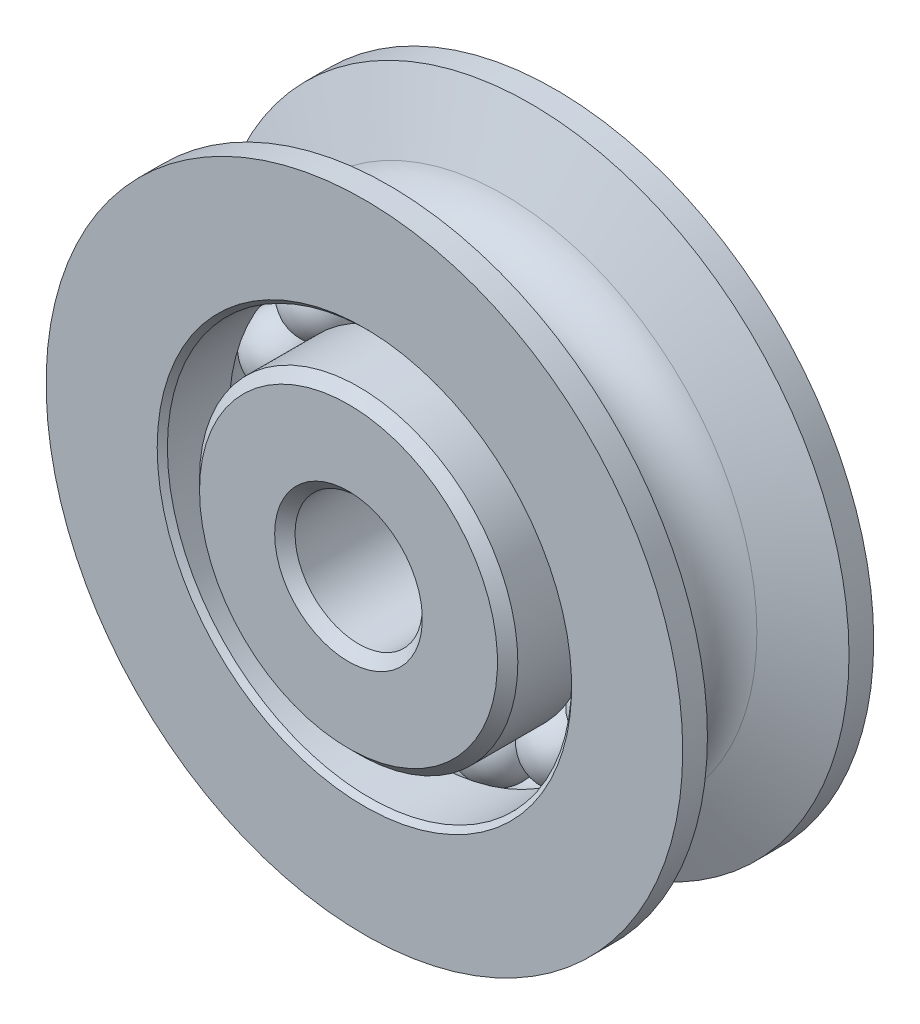
SolidWorks part; units mm, degrees
ref_plane "Front" through (0, 0, 0) normal (0, 0, 1) x (1, 0, 0)
ref_plane "Top" through (0, 0, 0) normal (0, 1, 0) x (1, 0, 0)
ref_plane "Right" through (0, 0, 0) normal (1, 0, 0) x (0, 0, -1)
sketch "Sketch1" plane through (0, 0, 0) normal (1, 0, 0) x (0, 0, -1)
  line L0 (3.5306, 15.875) -> (4.7625, 15.875)
  line L1 (-3.5306, 15.875) -> (-4.7625, 15.875)
  line L2 (-3.5306, 15.875) -> (-2.2078, 12.6016)
  line L3 (1.4287, 10.0806) -> (4.7625, 10.0806)
  line L4 (5.5562, 3.175) -> (-5.5562, 3.175)
  line L5 (-1.4287, 7.9375) -> (-5.5563, 7.9375)
  line L6 (3.5306, 15.875) -> (2.2078, 12.6016)
  line L8 (-5.5562, 0) -> (5.5562, 0) construction
  line L10 (4.7625, 15.875) -> (4.7625, 10.0806)
  line L13 (-5.5563, 7.9375) -> (-5.5562, 3.175)
  line L14 (0, 11.1125) -> (0, -11.1125) construction
  line L16 (5.5563, 7.9375) -> (5.5562, 3.175)
  line L17 (-4.7625, 15.875) -> (-4.7625, -15.875) construction
  line L18 (-4.7625, 10.0806) -> (-1.4287, 10.0806)
  line L20 (5.5563, 7.9375) -> (1.4287, 7.9375)
  line L21 (-4.7625, 10.0806) -> (-4.7625, 15.875)
  arc A0 (-2.2078, 12.6016) -> (2.2078, 12.6016) centre (0, 13.4938) ccw
  circle A1 centre (0, 13.4938) radius 2.3813 construction
  circle A2 centre (0, 0) radius 3.175 construction
  circle A3 centre (0, 0) radius 7.9375 construction
  arc A4 (-1.4287, 7.9375) -> (1.4287, 7.9375) centre (0, 9.0091) ccw
  circle A5 centre (0, -13.4937) radius 2.3813 construction
  arc A6 (1.4287, 10.0806) -> (-1.4287, 10.0806) centre (0, 9.0091) ccw
  point P28 (-4.7625, 0)
  dimension "Rope Dia" = 4.7625
  dimension "D1" = 15.875
  dimension "Shaft Dia" = 6.35
  dimension "D3" = 2.1431
  dimension "D2" = 3.5719
  dimension "Wd" = 11.1125
  dimension "D8" = 1.2319
  dimension "Groove Dia" = 22.225
  dimension "OD" = 31.75
  dimension "w Wd" = 9.525
revolve "Revolve1" add sketch "Sketch1" angle 360 about L8
sketch "Sketch2" plane through (0, 0, 0) normal (1, 0, 0) x (0, 0, -1)
  line L0 (0, 11.1125) -> (0, -11.1125) construction
  line L1 (0, 10.795) -> (0, 7.2231)
  arc A0 (1.4287, 10.0806) -> (-1.4287, 10.0806) centre (0, 9.0091) ccw construction
  arc A1 (0, 7.2231) -> (0, 10.795) centre (0, 9.0091) ccw
revolve "Revolve2" add sketch "Sketch2" angle 360 about L1
pattern_circular "CirPattern1" count 15 over 360 of bodies 117
chamfer "Chamfer1" distance 0.508 angle 45 4 edges at (3.175, 0, -5.5562) (7.9375, 0, -5.5563) (7.9375, 0, 5.5563) (3.175, 0, 5.5562)
chamfer "Chamfer2" distance 0.254 angle 45 2 edges at (10.0806, 0, -4.7625) (10.0806, 0, 4.7625)
equation "\"D1@Sketch1\" = \"Shaft Dia@Sketch1\" * 2.5"
equation "\"D2@Sketch1\" = \"Rope Dia@Sketch1\" * .75"
equation "\"D3@Sketch1\" = \"D2@Sketch1\" * .6"
